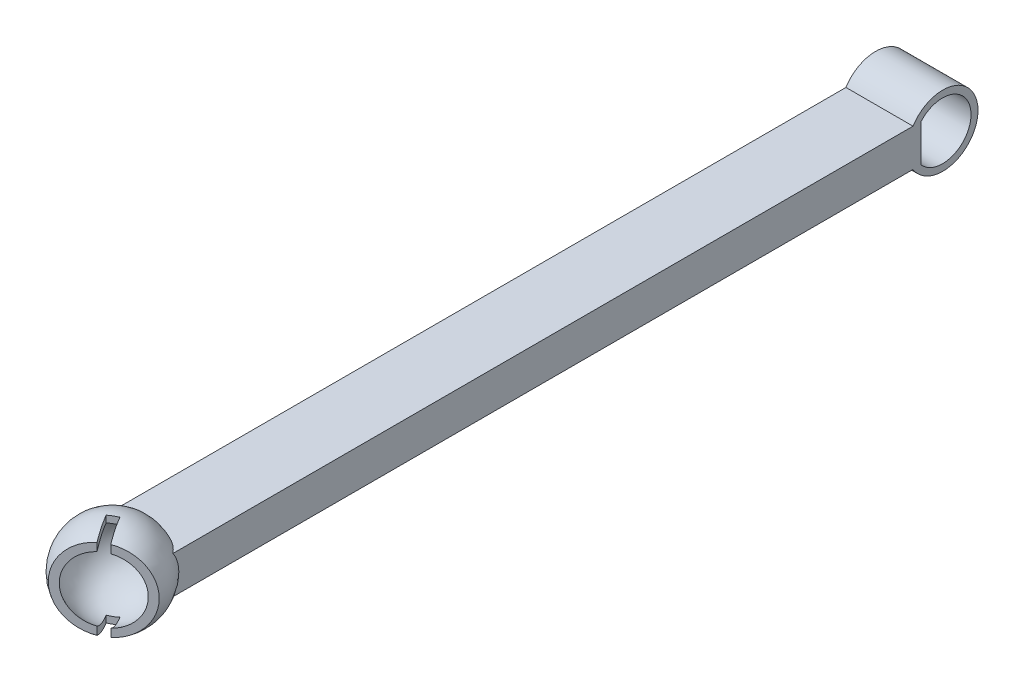
SolidWorks part; units mm, degrees
ref_plane "前视基准面" through (0, 0, 0) normal (0, 0, 1) x (1, 0, 0)
ref_plane "上视基准面" through (0, 0, 0) normal (0, 1, 0) x (1, 0, 0)
ref_plane "右视基准面" through (0, 0, 0) normal (1, 0, 0) x (0, 0, -1)
sketch "草图1" plane through (0, 0, 0) normal (0, 0, 1) x (1, 0, 0)
  line L1 (-10.406, -12.3317) -> (-2.406, -12.3317)
  line L2 (-10.406, -12.3317) -> (-10.406, -24.3317)
  line L3 (-10.406, -24.3317) -> (-2.406, -24.3317)
  line L4 (-2.406, -12.3317) -> (-2.406, -24.3317)
extrude "凸台-拉伸1" add sketch "草图1" along normal blind 100
sketch "草图5" plane through (-10.406, 0, 0) normal (-1, 0, 0) x (0, 0, 1)
  line L0 (0, -18.3317) -> (5, -18.3317)
  line L1 (0, -12.3317) -> (0, -24.3317) construction
  line L2 (100, -24.3317) -> (0, -24.3317) construction
  line L3 (0, -12.3317) -> (14.172, -12.3317)
  line L4 (0, -12.3317) -> (0, -24.3317)
  line L5 (0, -24.3317) -> (14.172, -24.3317)
  line L7 (7.5559, -16.0896) -> (7.5559, -20.5739)
  circle A0 centre (5, -18.3317) radius 3.4
extrude "切除-拉伸3" cut sketch "草图5" against normal blind 10 contours L7 A0 region at (-10.406, -18.3317, 7.4655)
sketch "草图2" plane through (-10.406, 0, 0) normal (-1, 0, 0) x (0, 0, 1)
  line L0 (100, -12.3317) -> (0, -12.3317) construction
  line L4 (-0.0119, -12.3317) -> (100, -12.3317)
  line L5 (7.5845, -16.0896) -> (100.0248, -16.0896)
  line L6 (7.5845, -16.0896) -> (7.5845, -20.5629)
  line L7 (7.5845, -20.5629) -> (100.0248, -20.5629)
  line L8 (100.0248, -16.0896) -> (100.0248, -20.5629)
  line L9 (100, -12.3317) -> (100.0248, -16.0896)
  line L10 (-0.0119, -12.3317) -> (-0.0119, -24.3317)
  line L11 (-0.0119, -24.3317) -> (22.5559, -24.3317)
  line L12 (100.0248, -20.5629) -> (100, -24.3317)
  line L13 (100, -24.3317) -> (22.5559, -24.3317)
  circle A2 centre (4.9707, -18.3317) radius 4.2
  point P0 (100, -24.3317)
  line M3 (0, -24.3317) -> (100, -24.3317)
  line M5 (100, -12.3317) -> (0, -12.3317)
extrude "切除-拉伸11" cut sketch "草图2" against normal blind 100 contours A2 L5 L7 M5 M3 region at (-10.406, -13.3393, -0.0059)
sketch "草图12" plane through (0, 0, 100) normal (0, 0, 1) x (1, 0, 0)
  line L0 (-6.406, -12.7263) -> (-6.406, -23.9263)
  arc A2 (-6.406, -13.5263) -> (-6.406, -23.1263) centre (-6.406, -18.3263) ccw
  arc A3 (-6.406, -12.7263) -> (-6.406, -23.9263) centre (-6.406, -18.3263) ccw
revolve "旋转3" add sketch "草图12" angle 360 about L0 region at (-6.5312, -13.1263, 100)
revolve "切除-旋转1" cut sketch "草图12<4>" angle 360 about L0 region at (-6.5134, -14.8079, 100) region at (-8.406, -18.3263, 100)
sketch "草图12<4>" plane through (0, 0, 100) normal (0, 0, 1) x (1, 0, 0) same geometry as "草图12"
ref_plane "基准面1" through (-52.3725, 0, 30.2373) normal (-0.866, 0, 0.5) x (0.5, 0, 0.866)
sketch "草图16" plane through (-52.3725, 0, 30.2373) normal (-0.866, 0, 0.5) x (0.5, 0, 0.866)
  line L0 (83.3995, -18.3263) -> (86.1995, -18.3263)
  line L1 (92.6293, -9.644) -> (82.7852, -9.644) construction
  line L2 (86.2123, -9.644) -> (92.6293, -9.644)
  line L3 (86.2123, -9.644) -> (86.2123, -29.1074)
  line L4 (86.2123, -29.1074) -> (92.6293, -29.1074)
  line L5 (92.6293, -9.644) -> (92.6293, -29.1074)
extrude "切除-拉伸14" cut sketch "草图16" against normal blind 18 and the other way blind 18 contours L5 L2 L3 | L5 L3 L4 | L3 region at (-7.6621, -19.3757, 107.678)
sketch "草图17" plane through (43.1062, 0, 74.6621) normal (0.5, 0, 0.866) x (0.866, 0, -0.5)
  line L0 (-56.1378, -23.9263) -> (-56.1378, -12.7263)
  line L1 (-56.1378, -23.9263) -> (-54.9378, -23.9263)
  line L2 (-56.1378, -12.7263) -> (-54.9378, -12.7263)
  line L3 (-54.9378, -23.9263) -> (-54.9378, -12.7263)
  line L4 (-56.1378, -23.9263) -> (-54.9378, -12.7263) construction
  line L5 (-56.1378, -12.7263) -> (-54.9378, -23.9263) construction
  point P0 (0, 0)
  point P1 (-55.5378, -18.3263)
extrude "切除-拉伸15" cut sketch "草图17" against normal blind 3
